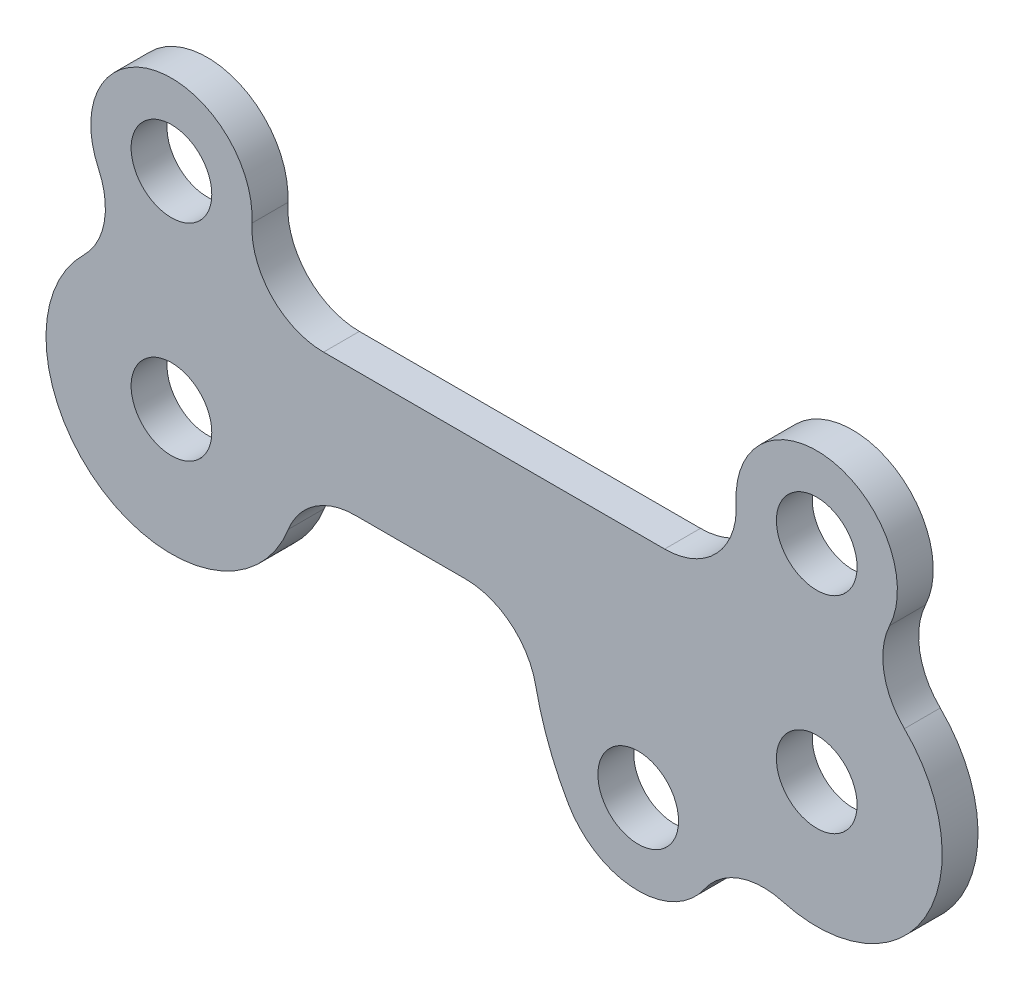
SolidWorks part; units mm, degrees
ref_plane "Front Plane" through (0, 0, 0) normal (0, 0, 1) x (1, 0, 0)
ref_plane "Top Plane" through (0, 0, 0) normal (0, 1, 0) x (1, 0, 0)
ref_plane "Right Plane" through (0, 0, 0) normal (1, 0, 0) x (0, 0, -1)
sketch "Sketch1" plane through (0, 0, 0) normal (0, 0, 1) x (1, 0, 0)
  line L0 (14.2875, 0) -> (-14.2875, 0)
  line L1 (-14.2875, 5.5563) -> (14.2875, 5.5563)
  line L2 (0, 5.5563) -> (0, 0)
  line L3 (6.3823, -4.5641) -> (14.2875, 0) construction
  circle A0 centre (-14.2875, 0) radius 1.7859
  circle A1 centre (-14.2875, 0) radius 5.5563
  circle A2 centre (-14.2875, 9.1281) radius 3.5719
  circle A3 centre (-14.2875, 9.1281) radius 1.7859
  circle A4 centre (-20.388, 6.2465) radius 3.175
  circle A5 centre (-7.5523, 8.7312) radius 3.175
  circle A6 centre (-1.2023, 8.7312) radius 3.175 construction
  circle A7 centre (-7.5523, 8.7312) radius 1.7859 construction
  circle A8 centre (7.5523, 8.7312) radius 1.7859 construction
  circle A9 centre (1.2023, 8.7312) radius 3.175 construction
  circle A10 centre (7.5523, 8.7312) radius 3.175
  circle A11 centre (20.388, 6.2465) radius 3.175
  circle A12 centre (14.2875, 9.1281) radius 1.7859
  circle A13 centre (14.2875, 9.1281) radius 3.5719
  circle A14 centre (14.2875, 0) radius 5.5563
  circle A15 centre (14.2875, 0) radius 1.7859
  circle A16 centre (6.3823, -4.5641) radius 3.5719
  circle A17 centre (6.3823, -4.5641) radius 1.7859
  arc A22 (1.5875, 0) -> (3.289, -6.35) centre (14.2875, 0) ccw
  dimension "D2" = 3.5719
  dimension "D3" = 11.1125
  dimension "D4" = 7.1437
  dimension "D5" = 6.35
  dimension "D1" = 14.2875
  dimension "D6" = 30
extrude "Boss-Extrude1" add sketch "Sketch1" along normal blind 1.5875 contours A1 A0 | A1 L0 L2 L1 | A4 A1 A2 | A5 A2 L1 | A2 A3 | L0 A14 L1 L2 | A15 A14 | L1 A13 A10 | A13 A12 | A13 A14 A11 | A16 A17 | L0 A22 A16 A14 region at (5.0393, 2.9628, 0) region at (4.4176, -1.3232, 0) region at (-5.0393, 2.9628, 0) region at (10.4698, 3.8177, 0) region at (4.6469, -1.5582, 0) region at (-16.3831, -4.9758, 0) region at (10.8545, 6.3075, 0) region at (11.9065, 6.6027, 0) region at (16.6309, 5.6656, 0) region at (-10.8545, 6.3075, 0) region at (-16.6309, 5.6656, 0) region at (-16.1451, 6.1962, 0)
fillet "Fillet1" radius 3.175 3 edges at (-8.7312, 0, 0.7937) (1.5875, 0, 0.7937) (9.4756, -2.7781, 0.7937)
